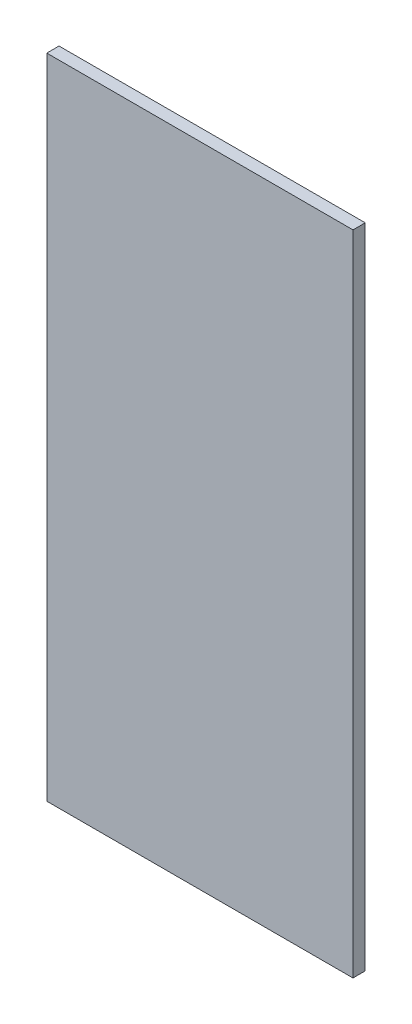
SolidWorks part; units mm, degrees
material "Perspex (TM) GS Acrylic Cast Sheet"
ref_plane "Front Plane" through (0, 0, 0) normal (0, 0, 1) x (1, 0, 0)
ref_plane "Top Plane" through (0, 0, 0) normal (0, 1, 0) x (1, 0, 0)
ref_plane "Right Plane" through (0, 0, 0) normal (1, 0, 0) x (0, 0, -1)
sketch "Sketch1" plane through (0, 0, 0) normal (0, 0, 1) x (1, 0, 0)
  line L1 (-75, -158.685) -> (75, -158.685)
  line L2 (-75, -158.685) -> (-75, 158.685)
  line L3 (-75, 158.685) -> (75, 158.685)
  line L4 (75, -158.685) -> (75, 158.685)
  line L5 (-75, -158.685) -> (75, 158.685) construction
  line L6 (-75, 158.685) -> (75, -158.685) construction
  point P0 (0, 0)
  dimension "D1" = 150
  dimension "D2" = 317.37
extrude "Boss-Extrude1" add sketch "Sketch1" along normal blind 6
equation "\"PCLength\"= 150mm'Length across I/O from PS to GPU"
equation "\"PCWidth\"= 340mm'Distance of longest part parallel to GPU(ussually GPU)"
equation "\"PCHeight\"= 190mm'Tallest point with mobo laying flat"
equation "\"WallThickness\"= 9mm'Thickness of each outer tank wall"
equation "\"ThermoBarrierThickness\"= 6mm'Thickness of barrier between hot side and cold side"
equation "\"HotSideGap\"= 15mm'Space in the hot side that hot fluid flows into"
equation "\"PCClearance\"= 40mm'Clearance from top of tank to top of PC"
equation "\"RadiatorHeight\"= 277.37mm'Final Height from ground of radiators"
equation "\"D1@Sketch1\"=\"PCLength\""
equation "\"D2@Sketch1\"=\"RadiatorHeight\" + 40"
equation "\"D1@Boss-Extrude1\"=\"ThermoBarrierThickness\""
